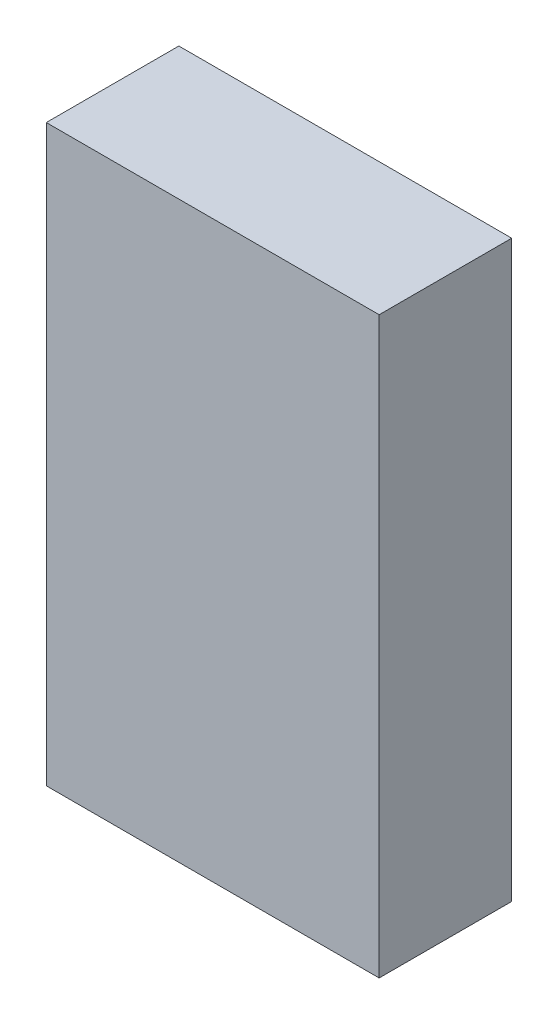
SolidWorks part; units mm, degrees
ref_plane "Спереди" through (0, 0, 0) normal (0, 0, 1) x (1, 0, 0)
ref_plane "Сверху" through (0, 0, 0) normal (0, 1, 0) x (1, 0, 0)
ref_plane "Справа" through (0, 0, 0) normal (1, 0, 0) x (0, 0, -1)
sketch "Эскиз1" plane through (0, 0, 0) normal (0, 0, 1) x (1, 0, 0)
  line L1 (-565, 975) -> (565, 975)
  line L2 (-565, 975) -> (-565, -975)
  line L3 (-565, -975) -> (565, -975)
  line L4 (565, 975) -> (565, -975)
  line L5 (-565, 975) -> (565, -975) construction
  line L6 (-565, -975) -> (565, 975) construction
  point P0 (0, 0)
extrude "Бобышка-Вытянуть1" add sketch "Эскиз1" along normal blind 450
sketch "Эскиз2" plane through (0, 0, 450) normal (0, 0, 1) x (1, 0, 0)
  line L0 (0, 975) -> (0, -975)
  text T0 "НТВ" font "Arial" height 80
  point P3 (-448.1337, 879.4072)
  point P6 (101.5001, 975)
  point P7 (0, 975)
  point P8 (0, -975)
  point P9 (0, -975)
  point P10 (0, -975)
  point P11 (0, -975)
  point P12 (0, 0)
  point P13 (0, -975)
  point P14 (0, -975)
  point P15 (0, 0)
  point P16 (0, 0)
  point P17 (0, -975)
